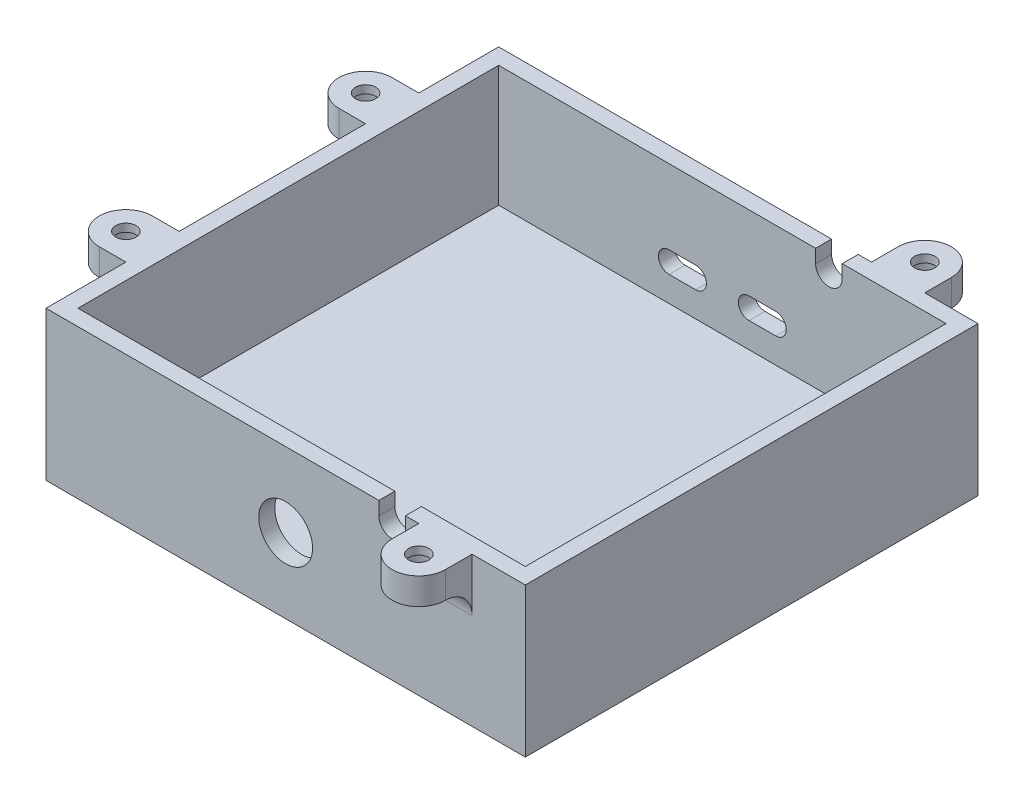
SolidWorks part; units mm, degrees
ref_plane "Front Plane" through (0, 0, 0) normal (0, 0, 1) x (1, 0, 0)
ref_plane "Top Plane" through (0, 0, 0) normal (0, 1, 0) x (1, 0, 0)
ref_plane "Right Plane" through (0, 0, 0) normal (1, 0, 0) x (0, 0, -1)
sketch "Sketch1" plane through (0, 0, 0) normal (0, 1, 0) x (1, 0, 0)
  line L1 (-45, 42.5) -> (45, 42.5)
  line L2 (-45, 42.5) -> (-45, -42.5)
  line L3 (-45, -42.5) -> (45, -42.5)
  line L4 (45, 42.5) -> (45, -42.5)
  line L5 (-45, 42.5) -> (45, -42.5) construction
  line L6 (-45, -42.5) -> (45, 42.5) construction
  point P0 (0, 0)
  dimension "D1" = 85
  dimension "D2" = 90
extrude "Boss-Extrude1" add sketch "Sketch1" along normal blind 28
shell "Shell1" thickness 3 removed face at (0, 28, 0)
sketch "Sketch2" plane through (0, 0, 42.5) normal (0, 0, 1) x (1, 0, 0)
  line L0 (-45, 14) -> (45, 14) construction
  line L1 (-45, 28) -> (-45, 0) construction
  line L2 (45, 28) -> (45, 0) construction
  circle A0 centre (0, 14) radius 5.05
  point P8 (0, 14)
  dimension "D1" = 10.1
extrude "Cut-Extrude1" cut sketch "Sketch2" against normal up to next
sketch "Sketch3" plane through (0, 28, 0) normal (0, 1, 0) x (1, 0, 0)
  line L0 (-45, 42.5) -> (-45, -42.5) construction
  line L1 (-50, 27.5) -> (-45, 27.5)
  line L2 (-50, 17.5) -> (-45, 17.5)
  line L3 (-45, 17.5) -> (-45, 27.5)
  line L4 (45, 42.5) -> (-45, 42.5) construction
  arc A0 (-50, 27.5) -> (-50, 17.5) centre (-50, 22.5) ccw
  dimension "D1" = 10
  dimension "D2" = 15
extrude "Boss-Extrude2" add sketch "Sketch3" against normal blind 5
mirror "Mirror1" about plane through (0, 0, 0) normal (0, 0, 1) of "Boss-Extrude2"
sketch "Sketch4" plane through (0, 28, 0) normal (0, 1, 0) x (1, 0, 0)
  line L0 (25, 47.5) -> (25, 42.5)
  line L1 (45, 42.5) -> (-45, 42.5) construction
  line L2 (25, 42.5) -> (35, 42.5)
  line L3 (35, 42.5) -> (35, 47.5)
  line L5 (45, -42.5) -> (45, 42.5) construction
  arc A0 (35, 47.5) -> (25, 47.5) centre (30, 47.5) ccw
  dimension "D1" = 10
  dimension "D2" = 10
extrude "Boss-Extrude3" add sketch "Sketch4" against normal blind 5
mirror "Mirror2" about plane through (0, 0, 0) normal (0, 0, 1) of "Boss-Extrude3"
hole_wizard "CBORE for #6 Socket Head Cap Screw1" positions "Sketch7" profile "Sketch8" counterbore size "#6" standard "ANSI Inch" end condition through all
sketch "Sketch7" plane through (0, 23, 0) normal (0, -1, 0) x (-1, 0, 0)
  point P0 (-30, 47.5)
  point P3 (-30, -47.5)
  point P6 (50, -22.5)
  point P9 (50, 22.5)
sketch "Sketch8" plane through (30, 23, -47.5) normal (1, 0, 0) x (0, 0, -1)
  line L0 (0, 0) -> (0, 5)
  line L1 (0, 5) -> (1.8986, 5)
  line L3 (1.8986, 5) -> (1.8986, 3.5052)
  line L4 (1.8986, 3.5052) -> (3.81, 3.5052)
  line L5 (3.81, 3.5052) -> (3.81, 0)
  line L7 (3.81, 0) -> (0, 0)
  line L11 (0, -6.35) -> (0, 107.95) construction
  dimension "Thru Hole Dia." = 3.7973
  dimension "Thru Hole Depth" = 5
  dimension "C'Bore Dia." = 7.62
  dimension "C'Bore Depth" = 3.5052
fillet "Fillet1" radius 5 4 edges at (30, 23, -42.5) (30, 23, 42.5) (-45, 23, -22.5) (-45, 23, 22.5)
sketch "Sketch9" plane through (0, 0, 42.5) normal (0, 0, 1) x (1, 0, 0)
  line L0 (20, 28) -> (20, 25.5) construction
  line L1 (-45, 28) -> (25, 28) construction
  line L2 (22.5, 28) -> (22.5, 25.5)
  line L3 (17.5, 28) -> (17.5, 25.5)
  arc A0 (22.5, 28) -> (17.5, 28) centre (20, 28) ccw
  arc A1 (17.5, 25.5) -> (22.5, 25.5) centre (20, 25.5) ccw
  point P4 (20, 26.75)
  dimension "D1" = 5
  dimension "D2" = 2.5
  dimension "D3" = 20
extrude "Cut-Extrude2" cut sketch "Sketch9" against normal through all
sketch "Sketch10" plane through (17.5, 0, -42.5) normal (0, 0, 1) x (1, 0, 0)
  line L0 (-27.5, 12) -> (-22.5, 12) construction
  line L1 (-27.5, 14) -> (-22.5, 14)
  line L2 (-27.5, 10) -> (-22.5, 10)
  line L3 (-17.5, 28) -> (-17.5, 0) construction
  line L4 (7.5, 28) -> (5, 28) construction
  line L5 (27.5, 0) -> (-62.5, 0) construction
  line L6 (-7.5, 12) -> (-12.5, 12) construction
  line L7 (-7.5, 14) -> (-12.5, 14)
  line L8 (-7.5, 10) -> (-12.5, 10)
  arc A0 (-27.5, 14) -> (-27.5, 10) centre (-27.5, 12) ccw
  arc A1 (-22.5, 10) -> (-22.5, 14) centre (-22.5, 12) ccw
  arc A2 (-7.5, 14) -> (-7.5, 10) centre (-7.5, 12) cw
  arc A3 (-12.5, 10) -> (-12.5, 14) centre (-12.5, 12) cw
  point P2 (-25, 12)
  point P7 (-25, 10)
  point P17 (-10, 12)
  dimension "D1" = 5
  dimension "D2" = 4
  dimension "D3" = 10
  dimension "D4" = 5
extrude "Cut-Extrude4" cut sketch "Sketch10" along normal up to next
equation "\"Mic Diameter\"=10.1"
equation "\"D1@Sketch2\"=\"Mic Diameter\""
